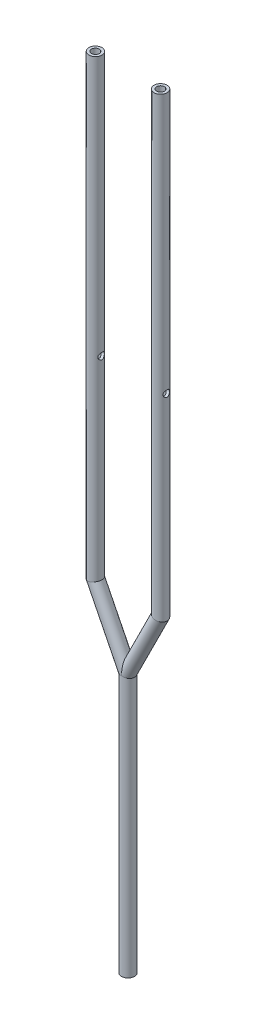
SolidWorks part; units mm, degrees
material "1060 Alloy"
ref_plane "Front Plane" through (0, 0, 0) normal (0, 0, 1) x (1, 0, 0)
ref_plane "Top Plane" through (0, 0, 0) normal (0, 1, 0) x (1, 0, 0)
ref_plane "Right Plane" through (0, 0, 0) normal (1, 0, 0) x (0, 0, -1)
sketch "Sketch1" plane through (0, 0, 0) normal (0, 0, 1) x (1, 0, 0)
  line L0 (0, 0) -> (-50, 0) construction
  line L1 (-50, 0) -> (0, 0) construction
  line L2 (0, 0) -> (0, -800) construction
  line L3 (-50, 0) -> (-50, -700)
  line L4 (-50, -700) -> (0, -800)
  line L5 (0, -800) -> (0, -1200)
  dimension "D1" = 50
  dimension "D2" = 800
  dimension "D3" = 700
  dimension "D4" = 400
sweep "Sweep1" add path "Sketch1" circular profile diameter 20 parameters "D3"=20
sketch "Sketch8" plane through (0, 0, 0) normal (0, 0, 1) x (1, 0, 0)
  line L2 (0, 0) -> (0, -800) construction
  line L3 (0, 0) -> (50, 0) construction
  line L4 (50, 0) -> (50, -700)
  line L5 (50, -700) -> (0, -800)
  dimension "D1" = 800
  dimension "D2" = 50
  dimension "D3" = 700
sweep "Sweep4" add path "Sketch8" circular profile diameter 20 parameters "D3"=20
shell "Shell1" thickness 4 removed face at (-10, -1200, 0) removed face at (40, 0, 0) removed face at (-60, 0, 0)
sketch "Sketch30" plane through (0, 0, 0) normal (1, 0, 0) x (0, 0, -1)
  line L0 (0, 0) -> (0, -400)
  circle A0 centre (0, -400) radius 5
  point P4 (0, 0)
  point P5 (0, 0)
  dimension "D2" = 10
  dimension "D1" = 400
extrude "Cut-Extrude1" cut sketch "Sketch30" against normal through all both and the other way through all contours A0
